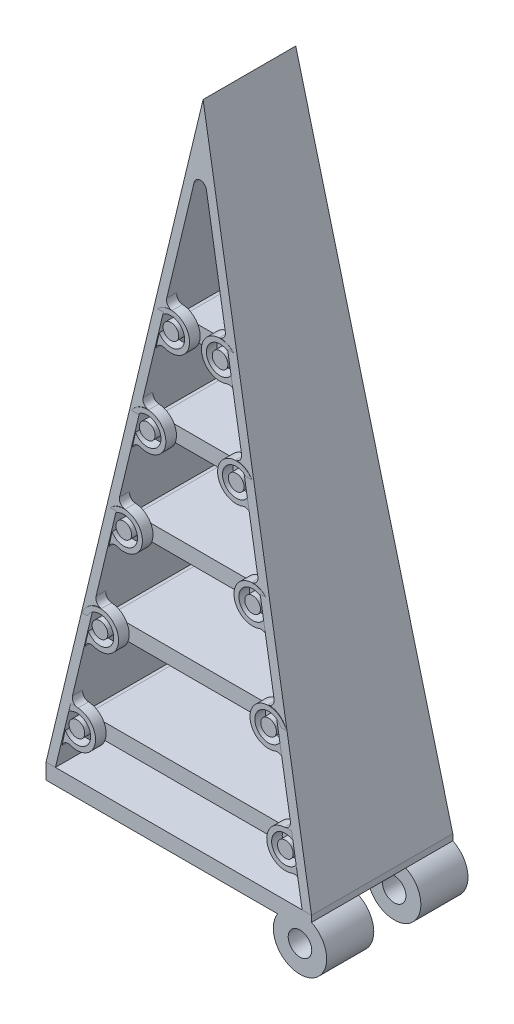
SolidWorks part; units mm, degrees
ref_plane "Ebene vorne" through (0, 0, 0) normal (0, 0, 1) x (1, 0, 0)
ref_plane "Ebene oben" through (0, 0, 0) normal (0, 1, 0) x (1, 0, 0)
ref_plane "Ebene rechts" through (0, 0, 0) normal (1, 0, 0) x (0, 0, -1)
ref_plane "Ebene7" through (0, 0, 9) normal (0, 0, 1) x (1, 0, 0)
sketch "Skizze1" plane through (0, 0, 0) normal (0, 0, 1) x (1, 0, 0)
  line L0 (0, 0) -> (16.9111, -80)
  line L1 (16.9111, -80) -> (15.7111, -80)
  line L2 (15.7111, -80) -> (0, -5.6767)
  line L3 (0, -5.6767) -> (-15.7111, -80)
  line L4 (-15.7111, -80) -> (-16.9111, -80)
  line L5 (-16.9111, -80) -> (0, 0)
  point P2 (-16.3111, -80)
  dimension "D1" = 1.2
  dimension "D2" = 1.2
  dimension "D3" = 23.872
  dimension "D4" = 80
extrude "Aufsatz-Linear austragen4" add sketch "Skizze1" along normal blind 18
ref_plane "Ebene8" through (17, 0, 0) normal (1, 0, 0) x (0, 0, -1)
sketch "Skizze11" plane through (17, 0, 0) normal (1, 0, 0) x (0, 0, -1)
  line L0 (-18, -80) -> (-14.9, 0)
  line L1 (-18, 0) -> (0, 0) construction
  line L2 (-14.9, 0) -> (-18, 0)
  line L3 (-18, 0) -> (-18, -80)
  line L4 (0, -80) -> (-3.1, 0)
  line L5 (-3.1, 0) -> (0, 0)
  line L6 (0, 0) -> (0, -80)
  dimension "D1" = 3.1
  dimension "D2" = 3.1
extrude "Schnitt-Linear austragen1" cut sketch "Skizze11" against normal through all
sketch "Skizze6" plane through (0, 0, 9) normal (0, 0, 1) x (1, 0, 0)
  line L1 (0, -5.6767) -> (-15.7111, -80) construction
  line L2 (15.7111, -80) -> (0, -5.6767) construction
  line L8 (3.1325, -25.6767) -> (-3.1325, -25.6767)
  line L11 (-3.1325, -27.6767) -> (3.1325, -27.6767)
  arc A0 (-3.1325, -25.6767) -> (-3.1325, -27.6767) centre (-3.1325, -26.6767) ccw
  arc A1 (3.1325, -25.6767) -> (3.1325, -27.6767) centre (3.1325, -26.6767) cw
  point P4 (-4.1325, -26.6767)
  point P9 (4.1325, -26.6767)
  dimension "D3" = 0.3
  dimension "D1" = 20
  dimension "D2" = 2
  dimension "D4" = 0.3
extrude "Aufsatz-Linear austragen5" add sketch "Skizze6" along normal blind 5.37 and the other way blind 5.37
sketch "Skizze7" plane through (0, 0, 9) normal (0, 0, 1) x (1, 0, 0)
  line L9 (5.6692, -37.6767) -> (-5.6692, -37.6767)
  line L12 (-5.6692, -39.6767) -> (5.6692, -39.6767)
  line L13 (-3.1325, -27.6767) -> (3.1325, -27.6767) construction
  line L14 (0, -5.6767) -> (-15.7111, -80) construction
  line L15 (15.7111, -80) -> (0, -5.6767) construction
  arc A0 (-5.6692, -37.6767) -> (-5.6692, -39.6767) centre (-5.6692, -38.6767) ccw
  arc A1 (5.6692, -37.6767) -> (5.6692, -39.6767) centre (5.6692, -38.6767) cw
  point P3 (-6.6692, -38.6767)
  point P10 (6.6692, -38.6767)
  dimension "D3" = 0.3
  dimension "D1" = 10
  dimension "D2" = 2
  dimension "D4" = 0.3
extrude "Aufsatz-Linear austragen6" add sketch "Skizze7" along normal blind 5.85 and the other way blind 5.85
sketch "Skizze8" plane through (0, 0, 9) normal (0, 0, 1) x (1, 0, 0)
  line L9 (8.2059, -49.6767) -> (-8.2059, -49.6767)
  line L12 (-8.2059, -51.6767) -> (8.2059, -51.6767)
  line L13 (-5.6692, -39.6767) -> (5.6692, -39.6767) construction
  line L14 (0, -5.6767) -> (-15.7111, -80) construction
  line L15 (15.7111, -80) -> (0, -5.6767) construction
  arc A0 (-8.2059, -49.6767) -> (-8.2059, -51.6767) centre (-8.2059, -50.6767) ccw
  arc A1 (8.2059, -49.6767) -> (8.2059, -51.6767) centre (8.2059, -50.6767) cw
  point P6 (-9.2059, -50.6767)
  point P11 (9.2059, -50.6767)
  dimension "D3" = 0.3
  dimension "D1" = 10
  dimension "D2" = 2
  dimension "D4" = 0.3
extrude "Aufsatz-Linear austragen7" add sketch "Skizze8" along normal blind 6.3 and the other way blind 6.3
sketch "Skizze9" plane through (0, 0, 9) normal (0, 0, 1) x (1, 0, 0)
  line L9 (10.7426, -61.6767) -> (-10.7426, -61.6767)
  line L12 (-10.7426, -63.6767) -> (10.7426, -63.6767)
  line L13 (-8.2059, -51.6767) -> (8.2059, -51.6767) construction
  line L14 (0, -5.6767) -> (-15.7111, -80) construction
  line L15 (15.7111, -80) -> (0, -5.6767) construction
  arc A0 (-10.7426, -61.6767) -> (-10.7426, -63.6767) centre (-10.7426, -62.6767) ccw
  arc A1 (10.7426, -61.6767) -> (10.7426, -63.6767) centre (10.7426, -62.6767) cw
  point P3 (-11.7426, -62.6767)
  point P10 (11.7426, -62.6767)
  dimension "D3" = 0.3
  dimension "D1" = 10
  dimension "D2" = 2
  dimension "D4" = 0.3
extrude "Aufsatz-Linear austragen8" add sketch "Skizze9" along normal blind 6.8 and the other way blind 6.8
sketch "Skizze10" plane through (0, 0, 9) normal (0, 0, 1) x (1, 0, 0)
  line L9 (13.2792, -73.6767) -> (-13.2792, -73.6767)
  line L12 (-13.2792, -75.6767) -> (13.2792, -75.6767)
  line L13 (-10.7426, -63.6767) -> (10.7426, -63.6767) construction
  line L14 (0, -5.6767) -> (-15.7111, -80) construction
  line L15 (15.7111, -80) -> (0, -5.6767) construction
  arc A0 (-13.2792, -73.6767) -> (-13.2792, -75.6767) centre (-13.2792, -74.6767) ccw
  arc A1 (13.2792, -73.6767) -> (13.2792, -75.6767) centre (13.2792, -74.6767) cw
  point P3 (-14.2792, -74.6767)
  point P10 (14.2792, -74.6767)
  dimension "D3" = 0.3
  dimension "D1" = 10
  dimension "D2" = 2
  dimension "D4" = 0.3
extrude "Aufsatz-Linear austragen9" add sketch "Skizze10" along normal blind 7.2 and the other way blind 7.2
sketch "Skizze13" plane through (0, 0, 14.37) normal (0, 0, 1) x (1, 0, 0)
  circle A0 centre (-3.1325, -26.6767) radius 1
  circle A1 centre (3.1325, -26.6767) radius 1
  dimension "D1" = 2
  dimension "D2" = 2
extrude "Aufsatz-Linear austragen12" add sketch "Skizze13" along normal blind 1.5
sketch "Skizze14" plane through (0, 0, 14.85) normal (0, 0, 1) x (1, 0, 0)
  circle A0 centre (-5.6692, -38.6767) radius 1
  circle A1 centre (5.6692, -38.6767) radius 1
extrude "Aufsatz-Linear austragen13" add sketch "Skizze14" along normal blind 1.5
sketch "Skizze15" plane through (0, 0, 15.3) normal (0, 0, 1) x (1, 0, 0)
  circle A0 centre (-8.2059, -50.6767) radius 1
  circle A1 centre (8.2059, -50.6767) radius 1
extrude "Aufsatz-Linear austragen14" add sketch "Skizze15" along normal blind 1.5
sketch "Skizze16" plane through (0, 0, 15.8) normal (0, 0, 1) x (1, 0, 0)
  circle A0 centre (-10.7426, -62.6767) radius 1
  circle A1 centre (10.7426, -62.6767) radius 1
extrude "Aufsatz-Linear austragen15" add sketch "Skizze16" along normal blind 1.5
sketch "Skizze17" plane through (0, 0, 16.2) normal (0, 0, 1) x (1, 0, 0)
  circle A0 centre (-13.2792, -74.6767) radius 1
  circle A1 centre (13.2792, -74.6767) radius 1
extrude "Aufsatz-Linear austragen16" add sketch "Skizze17" along normal blind 1.5
sketch "Skizze18" plane through (0, 0, 3.63) normal (0, 0, -1) x (-1, 0, 0)
  circle A0 centre (-3.1325, -26.6767) radius 1
  circle A1 centre (3.1325, -26.6767) radius 1
extrude "Aufsatz-Linear austragen17" add sketch "Skizze18" along normal blind 1.5
sketch "Skizze19" plane through (0, 0, 3.15) normal (0, 0, -1) x (-1, 0, 0)
  circle A0 centre (-5.6692, -38.6767) radius 1
  circle A1 centre (5.6692, -38.6767) radius 1
extrude "Aufsatz-Linear austragen18" add sketch "Skizze19" along normal blind 1.5
sketch "Skizze20" plane through (0, 0, 2.7) normal (0, 0, -1) x (-1, 0, 0)
  circle A0 centre (-8.2059, -50.6767) radius 1
  circle A1 centre (8.2059, -50.6767) radius 1
extrude "Aufsatz-Linear austragen19" add sketch "Skizze20" along normal blind 1.5
sketch "Skizze21" plane through (0, 0, 2.2) normal (0, 0, -1) x (-1, 0, 0)
  circle A0 centre (-10.7426, -62.6767) radius 1
  circle A1 centre (10.7426, -62.6767) radius 1
extrude "Aufsatz-Linear austragen20" add sketch "Skizze21" along normal blind 1.5
sketch "Skizze22" plane through (0, 0, 1.8) normal (0, 0, -1) x (-1, 0, 0)
  circle A0 centre (-13.2792, -74.6767) radius 1
  circle A1 centre (13.2792, -74.6767) radius 1
extrude "Aufsatz-Linear austragen21" add sketch "Skizze22" along normal blind 1.5
sketch "Skizze24" plane through (0, 0, 15.87) normal (0, 0, 1) x (1, 0, 0)
  circle A0 centre (-3.1325, -26.6767) radius 1.75
  circle A1 centre (-3.1325, -26.6767) radius 2.375
  circle A2 centre (3.1325, -26.6767) radius 1.75
  circle A3 centre (3.1325, -26.6767) radius 2.375
  dimension "D1" = 3.5
  dimension "D2" = 4.75
  dimension "D3" = 3.5
  dimension "D4" = 4.75
extrude "Aufsatz-Linear austragen22" add sketch "Skizze24" against normal blind 1.35
sketch "Skizze25" plane through (0, 0, 16.35) normal (0, 0, 1) x (1, 0, 0)
  circle A0 centre (-5.6692, -38.6767) radius 1.75
  circle A1 centre (-5.6692, -38.6767) radius 2.375
  circle A2 centre (5.6692, -38.6767) radius 1.75
  circle A3 centre (5.6692, -38.6767) radius 2.375
  dimension "D1" = 3.5
  dimension "D2" = 4.75
  dimension "D3" = 3.5
  dimension "D4" = 4.75
extrude "Aufsatz-Linear austragen23" add sketch "Skizze25" against normal blind 1.35
sketch "Skizze26" plane through (0, 0, 16.8) normal (0, 0, 1) x (1, 0, 0)
  circle A0 centre (-8.2059, -50.6767) radius 1.75
  circle A1 centre (-8.2059, -50.6767) radius 2.375
  circle A2 centre (8.2059, -50.6767) radius 1.75
  circle A3 centre (8.2059, -50.6767) radius 2.375
  dimension "D1" = 3.5
  dimension "D2" = 4.75
  dimension "D3" = 3.5
  dimension "D4" = 4.75
extrude "Aufsatz-Linear austragen24" add sketch "Skizze26" against normal blind 1.35
sketch "Skizze27" plane through (0, 0, 17.3) normal (0, 0, 1) x (1, 0, 0)
  circle A0 centre (-10.7426, -62.6767) radius 1.75
  circle A1 centre (-10.7426, -62.6767) radius 2.375
  circle A2 centre (10.7426, -62.6767) radius 1.75
  circle A3 centre (10.7426, -62.6767) radius 2.375
  dimension "D1" = 3.5
  dimension "D2" = 4.75
  dimension "D3" = 3.5
  dimension "D4" = 4.75
extrude "Aufsatz-Linear austragen25" add sketch "Skizze27" against normal blind 1.35
sketch "Skizze28" plane through (0, 0, 17.7) normal (0, 0, 1) x (1, 0, 0)
  circle A0 centre (-13.2792, -74.6767) radius 1.75
  circle A1 centre (-13.2792, -74.6767) radius 2.375
  circle A2 centre (13.2792, -74.6767) radius 1.75
  circle A3 centre (13.2792, -74.6767) radius 2.375
  dimension "D1" = 3.5
  dimension "D2" = 4.75
  dimension "D3" = 3.5
  dimension "D4" = 4.75
extrude "Aufsatz-Linear austragen26" add sketch "Skizze28" against normal blind 1.35
sketch "Skizze29" plane through (0, 0, 2.13) normal (0, 0, -1) x (-1, 0, 0)
  circle A0 centre (-3.1325, -26.6767) radius 1.75
  circle A1 centre (-3.1325, -26.6767) radius 2.375
  circle A2 centre (3.1325, -26.6767) radius 1.75
  circle A3 centre (3.1325, -26.6767) radius 2.375
extrude "Aufsatz-Linear austragen27" add sketch "Skizze29" against normal blind 1.35
sketch "Skizze30" plane through (0, 0, 1.65) normal (0, 0, -1) x (-1, 0, 0)
  circle A0 centre (-5.6692, -38.6767) radius 1.75
  circle A1 centre (-5.6692, -38.6767) radius 2.375
  circle A2 centre (5.6692, -38.6767) radius 1.75
  circle A3 centre (5.6692, -38.6767) radius 2.375
extrude "Aufsatz-Linear austragen28" add sketch "Skizze30" against normal blind 1.35
sketch "Skizze31" plane through (0, 0, 1.2) normal (0, 0, -1) x (-1, 0, 0)
  circle A0 centre (-8.2059, -50.6767) radius 1.75
  circle A1 centre (-8.2059, -50.6767) radius 2.375
  circle A2 centre (8.2059, -50.6767) radius 1.75
  circle A3 centre (8.2059, -50.6767) radius 2.375
extrude "Aufsatz-Linear austragen29" add sketch "Skizze31" against normal blind 1.35
sketch "Skizze32" plane through (0, 0, 0.7) normal (0, 0, -1) x (-1, 0, 0)
  circle A0 centre (-10.7426, -62.6767) radius 1.75
  circle A1 centre (-10.7426, -62.6767) radius 2.375
  circle A2 centre (10.7426, -62.6767) radius 1.75
  circle A3 centre (10.7426, -62.6767) radius 2.375
extrude "Aufsatz-Linear austragen30" add sketch "Skizze32" against normal blind 1.35
sketch "Skizze33" plane through (0, 0, 0.3) normal (0, 0, -1) x (-1, 0, 0)
  circle A0 centre (-13.2792, -74.6767) radius 1.75
  circle A1 centre (-13.2792, -74.6767) radius 2.375
  circle A2 centre (13.2792, -74.6767) radius 1.75
  circle A3 centre (13.2792, -74.6767) radius 2.375
extrude "Aufsatz-Linear austragen31" add sketch "Skizze33" against normal blind 1.35
fillet "Verrundung1" radius 0.8 1 edges at (0, -5.6767, 9)
fillet "Verrundung2" radius 0.8 40 edges at (12.4073, -64.3707, 16.625) (9.8706, -52.3707, 16.125) (7.3339, -40.3707, 15.675) (4.7973, -28.3707, 15.195) (-4.7973, -28.3707, 15.195) (-7.3339, -40.3707, 15.675) (-9.8706, -52.3707, 16.125) (-12.4073, -64.3707, 16.625) (-14.9439, -76.3707, 17.025) (14.9439, -76.3707, 17.025) (14.116, -72.454, 17.025) (-14.116, -72.454, 17.025) (-11.5793, -60.454, 16.5963) (11.5793, -60.454, 16.5963) (9.0427, -48.454, 16.1138) (-9.0427, -48.454, 16.1138) (-6.506, -36.454, 15.6563) (6.506, -36.454, 15.6563) (3.9693, -24.454, 15.1838) (-3.9693, -24.454, 15.1838) (-7.3339, -40.3707, 2.325) (-4.7973, -28.3707, 2.805) (-3.9693, -24.454, 2.8162) (-6.506, -36.454, 2.3437) (-9.0427, -48.454, 1.8862) (-9.8706, -52.3707, 1.875) (-12.4073, -64.3707, 1.375) (-11.5793, -60.454, 1.4037) (-14.116, -72.454, 0.975) (-14.9439, -76.3707, 0.975) (14.9439, -76.3707, 0.975) (14.116, -72.454, 0.975) (12.4073, -64.3707, 1.375) (11.5793, -60.454, 1.4037) (9.8706, -52.3707, 1.875) (9.0427, -48.454, 1.8862) (7.3339, -40.3707, 2.325) (6.506, -36.454, 2.3437) (4.7973, -28.3707, 2.805) (3.9693, -24.454, 2.8162)
sketch "Skizze37" plane through (0, -80, 0) normal (0, -1, 0) x (1, 0, 0)
  line L0 (-16.9111, 0) -> (-15.7111, 0)
  line L1 (-15.7111, 0) -> (16.9111, 0)
  line L2 (16.9111, 0) -> (16.9111, 18)
  line L3 (16.9111, 18) -> (-16.9111, 18)
  line L4 (-16.9111, 18) -> (-16.9111, 0)
  point P4 (16.9111, 0)
  point P11 (16.9111, 0)
  point P12 (0, 0)
  point P13 (16.9111, 0)
extrude "Aufsatz-Linear austragen32" add sketch "Skizze37" along normal blind 2
sketch "Skizze38" plane through (0, 0, 18) normal (0, 0, 1) x (1, 0, 0)
  circle A0 centre (15.4414, -83.854) radius 3.4
extrude "Aufsatz-Linear austragen33" add sketch "Skizze38" against normal blind 18
sketch "Skizze39" plane through (0, 0, 18) normal (0, 0, 1) x (1, 0, 0)
  circle A0 centre (15.4414, -83.854) radius 1.5
extrude "Schnitt-Linear austragen2" cut sketch "Skizze39" against normal blind 18
sketch "Skizze40" plane through (0, 0, 18) normal (0, 0, 1) x (1, 0, 0)
  circle A0 centre (15.4414, -83.854) radius 3.4
  point P3 (0, 0)
  point P4 (15.4414, -83.854)
extrude "Schnitt-Linear austragen3" cut sketch "Skizze40" against normal blind 6 from offset 6 offset against normal yes
sketch "Skizze42" plane through (0, -82, 0) normal (0, -1, 0) x (1, 0, 0)
  circle A0 centre (-14.5497, 9.2939) radius 0.5
extrude "Schnitt-Linear austragen4" cut sketch "Skizze42" against normal blind 2
sketch "Skizze43" plane through (0, -82, 0) normal (0, -1, 0) x (1, 0, 0)
  line L1 (-13.9679, 8.351) -> (11.3804, 8.351)
  line L2 (-13.9679, 8.351) -> (-13.9679, 10.3734)
  line L3 (-13.9679, 10.3734) -> (11.3804, 10.3734)
  line L4 (11.3804, 8.351) -> (11.3804, 10.3734)
extrude "Aufsatz-Linear austragen34" add sketch "Skizze43" along normal blind 2
fillet "Verrundung3" radius 1 1 edges at (-13.9679, -84, 9.3622)
sketch "Skizze44" plane through (11.3804, 0, 0) normal (1, 0, 0) x (0, 0, -1)
  line L0 (-8.351, -84) -> (-10.3734, -84) construction
  circle A0 centre (-9.3622, -84) radius 0.6176
extrude "Schnitt-Linear austragen5" cut sketch "Skizze44" against normal blind 32
sketch "Skizze45" plane through (0, -84, 0) normal (0, -1, 0) x (1, 0, 0)
  line L1 (11.3804, 10.3734) -> (-12.9679, 10.3734) construction
  line L2 (-12.9679, 8.351) -> (11.3804, 8.351) construction
  line L6 (-12.9679, 10.3734) -> (-12.9679, 8.351)
  line L7 (-12.9679, 8.351) -> (-11.9659, 8.351)
  line L8 (-11.9659, 8.351) -> (-11.9659, 10.3734)
  line L9 (-11.9659, 10.3734) -> (-12.9679, 10.3734)
  line L10 (9.2026, 8.351) -> (9.2026, 10.3734)
  line L11 (9.2026, 10.3734) -> (8.5252, 10.3734)
  line L12 (8.5252, 10.3734) -> (8.5252, 8.351)
  line L13 (8.5252, 8.351) -> (9.2026, 8.351)
extrude "Aufsatz-Linear austragen35" add sketch "Skizze45" along normal blind 0.5
